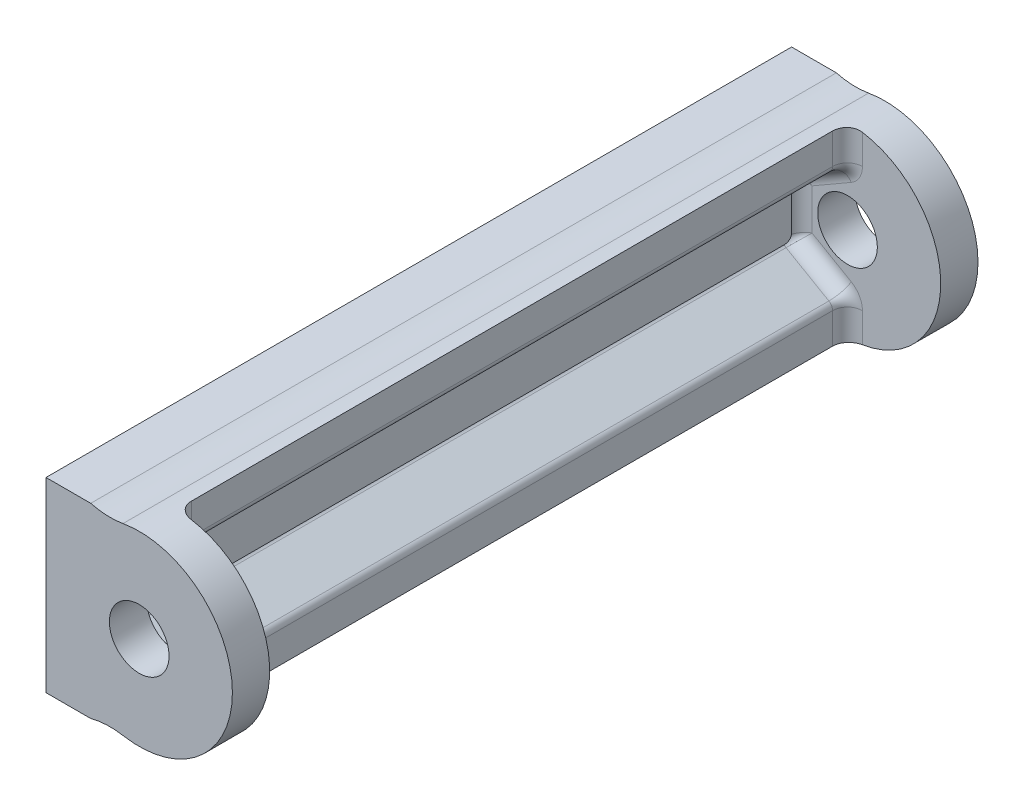
SolidWorks part; units mm, degrees
ref_plane "Front Plane" through (0, 0, 0) normal (0, 0, 1) x (1, 0, 0)
ref_plane "Top Plane" through (0, 0, 0) normal (0, 1, 0) x (1, 0, 0)
ref_plane "Right Plane" through (0, 0, 0) normal (1, 0, 0) x (0, 0, -1)
sketch "Sketch1" plane through (0, 0, 0) normal (0, 0, 1) x (1, 0, 0)
  circle A0 centre (0, 0) radius 12.5
  dimension "D1" = 25
extrude "Boss-Extrude1" add sketch "Sketch1" along normal blind 100
ref_plane "Plane1" through (0, 0, 95) normal (0, 0, 1) x (1, 0, 0)
sketch "Sketch3" plane through (0, 0, 95) normal (0, 0, 1) x (1, 0, 0)
  line L0 (0, 0) -> (0, 12.5) construction
  line L10 (0, 0) -> (0, -12.5) construction
  line L12 (0, 7.7942) -> (-6.75, 3.8971)
  line L13 (-6.75, 3.8971) -> (-6.75, -3.8971)
  line L17 (-6.75, -3.8971) -> (0, -7.7942)
  line L18 (0, -7.7942) -> (6.75, -3.8971)
  line L19 (6.75, -3.8971) -> (6.75, 3.8971)
  line L20 (6.75, 3.8971) -> (0, 7.7942)
  circle A0 centre (0, 0) radius 12.5 construction
  circle A1 centre (0, 0) radius 6.75 construction
  dimension "D1" = 13.5
extrude "Cut-Extrude1" cut sketch "Sketch3" against normal blind 90
sketch "Sketch4" plane through (0, 0, 95) normal (0, 0, 1) x (1, 0, 0)
  circle A0 centre (0, 0) radius 4
  dimension "D1" = 8
extrude "Cut-Extrude2" cut sketch "Sketch4" against normal through all both and the other way through all
sketch "Sketch5" plane through (0, 0, 95) normal (0, 0, 1) x (1, 0, 0)
  line L0 (0, 0) -> (0, 14)
  line L1 (0, 14) -> (18.187, 14)
  line L2 (18.187, 14) -> (18.187, -14)
  line L3 (18.187, -14) -> (0, -14)
  line L4 (0, -14) -> (0, 0)
  dimension "D1" = 14
  dimension "D2" = 28
extrude "Cut-Extrude3" cut sketch "Sketch5" against normal blind 90
fillet "Fillet9" radius 1 4 edges at (0, -7.7942, 50) (-6.75, -3.8971, 50) (0, 7.7942, 50) (-6.75, 3.8971, 50)
fillet "Fillet11" radius 2 18 edges at (0, 10.4358, 5) (-0.134, 7.8716, 5) (-3.375, 5.8457, 5) (-6.616, 3.8198, 5) (-6.75, 0, 5) (-6.616, -3.8198, 5) (-3.375, -5.8457, 5) (-0.134, -7.8716, 5) (0, -10.4358, 5) (-6.616, 3.8198, 95) (-0.134, 7.8716, 95) (0, 10.4358, 95) (-3.375, 5.8457, 95) (-6.616, -3.8198, 95) (-6.75, 0, 95) (-0.134, -7.8716, 95) (-3.375, -5.8457, 95) (0, -10.4358, 95)
sketch "Sketch6" plane through (0, 0, 100) normal (0, 0, 1) x (1, 0, 0)
  line L3 (-6.5, -12.5) -> (-12.5, -12.5)
  line L4 (-12.5, 0) -> (-12.5, -12.5)
  line L11 (-6.5, 12.5) -> (-12.5, 12.5)
  line L12 (-12.5, 0) -> (-12.5, 12.5)
  line L13 (-6.5, -12.5) -> (-6.5, 12.5)
  circle A0 centre (0, 0) radius 12.5 construction
  dimension "D1" = 6
  dimension "D2" = 25
extrude "Boss-Extrude2" add sketch "Sketch6" against normal through all
fillet "Fillet12" radius 10 2 edges at (-6.5, -10.6771, 50) (-6.5, 10.6771, 50)
